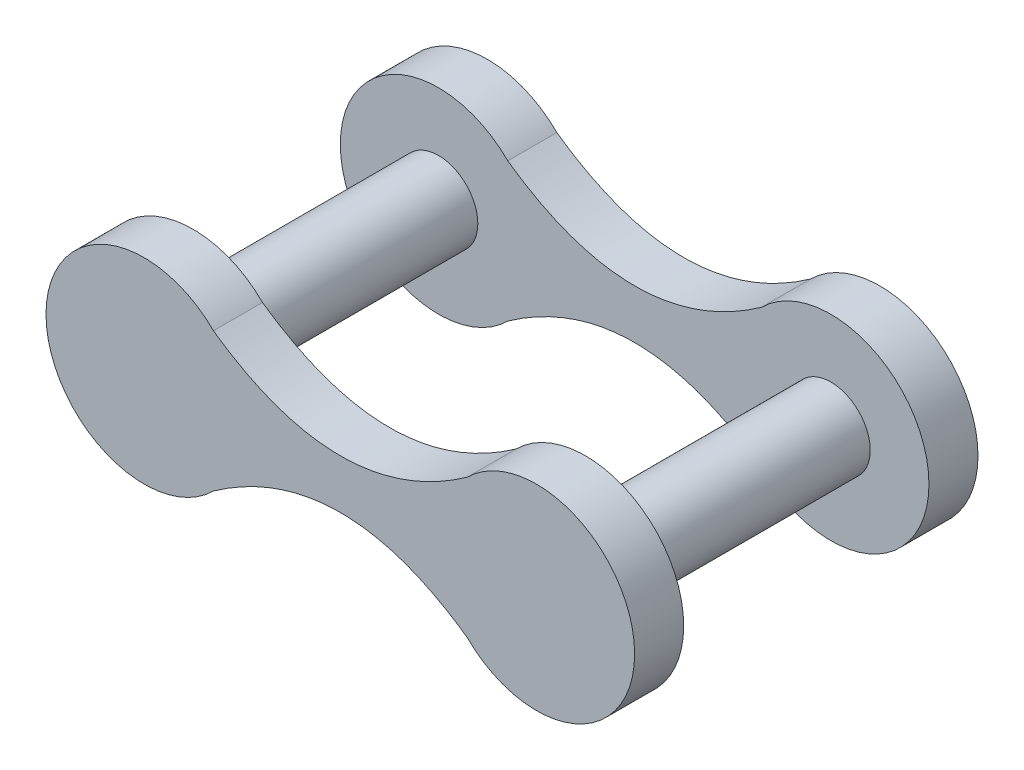
SolidWorks part; units mm, degrees
ref_plane "Front Plane" through (0, 0, 0) normal (0, 0, 1) x (1, 0, 0)
ref_plane "Top Plane" through (0, 0, 0) normal (0, 1, 0) x (1, 0, 0)
ref_plane "Right Plane" through (0, 0, 0) normal (1, 0, 0) x (0, 0, -1)
sketch "Sketch1" plane through (0, 0, 0) normal (0, 0, 1) x (1, 0, 0)
  line L0 (-6.35, 0) -> (6.35, 0) construction
  line L1 (-6.35, 0) -> (-6.35, 5.3941) construction
  line L2 (0, -9.5021) -> (0, 10.9777) construction
  line L3 (-6.35, 0) -> (0, 6.35) construction
  line L4 (0, 6.35) -> (6.35, 0) construction
  line L5 (-2.1004, 0.7937) -> (1.9982, 0.7937) construction
  arc A0 (-4.1049, 2.2451) -> (-4.1049, -2.2451) centre (-6.35, 0) ccw
  arc A1 (4.1049, -2.2451) -> (4.1049, 2.2451) centre (6.35, 0) ccw
  spline S0 degree 2 poles (-4.1049, 2.2451) (0, -0.6576) (4.1049, 2.2451) knots 0 0 0 1 1 1
  spline S1 degree 2 poles (-4.1049, -2.2451) (0, 0.6576) (4.1049, -2.2451) knots 0 0 0 1 1 1
  point P7 (-4.1049, 2.2451)
  point P12 (4.1049, 2.2451)
  dimension "D1" = 6.35
  dimension "D2" = 6.35
  dimension "D3" = 12.7
  dimension "D4" = 0.7937
extrude "Boss-Extrude1" add sketch "Sketch1" along normal blind 1.5875
sketch "Sketch2" plane through (0, 0, 1.5875) normal (0, 0, 1) x (1, 0, 0)
  line L0 (0, 3.0728) -> (0, -3.9301) construction
  line L1 (0, -9.5021) -> (0, 10.9777) construction
  circle A0 centre (-6.35, 0) radius 1.2753
  circle A1 centre (6.35, 0) radius 1.2753
  point P2 (6.35, 0)
extrude "Boss-Extrude2" add sketch "Sketch2" along normal blind 7.9375
ref_plane "chianplane" through (0, 0, 5.5563) normal (0, 0, 1) x (1, 0, 0)
mirror "Mirror1" about plane through (0, 0, 5.5563) normal (0, 0, 1) of "Boss-Extrude1"
scale "Scale1" scale about centroid uniform scaling yes scale factor 0.75
equation "\"large_diameter\" = 1/4in"
equation "\"small_diameter\" = 1/8in"
equation "\"arc_height\" = 1/32in"
equation "\"chain_space\" = 1/2in"
equation "\"chain_thickness\" = 1/16in"
equation "\"outer_height\" = 3/16in"
equation "\"inner_height\" = 2/16in"
equation "\"D1@Sketch1\" = \"large_diameter\""
equation "\"D2@Sketch1\" = \"large_diameter\""
equation "\"D3@Sketch1\"= \"chain_space\""
equation "\"D4@Sketch1\"= \"arc_height\""
equation "\"D1@Boss-Extrude1\"=\"chain_thickness\"\""
equation "\"D1@Boss-Extrude2\" = \"inner_height\" + 2 * \"chain_thickness\" + \"give\""
equation "\"give\" = 1/16in"
equation "\"D1@chianplane\" =  ( \"inner_height\" + 2 * \"chain_thickness\" + \"give\" )  / 2"
